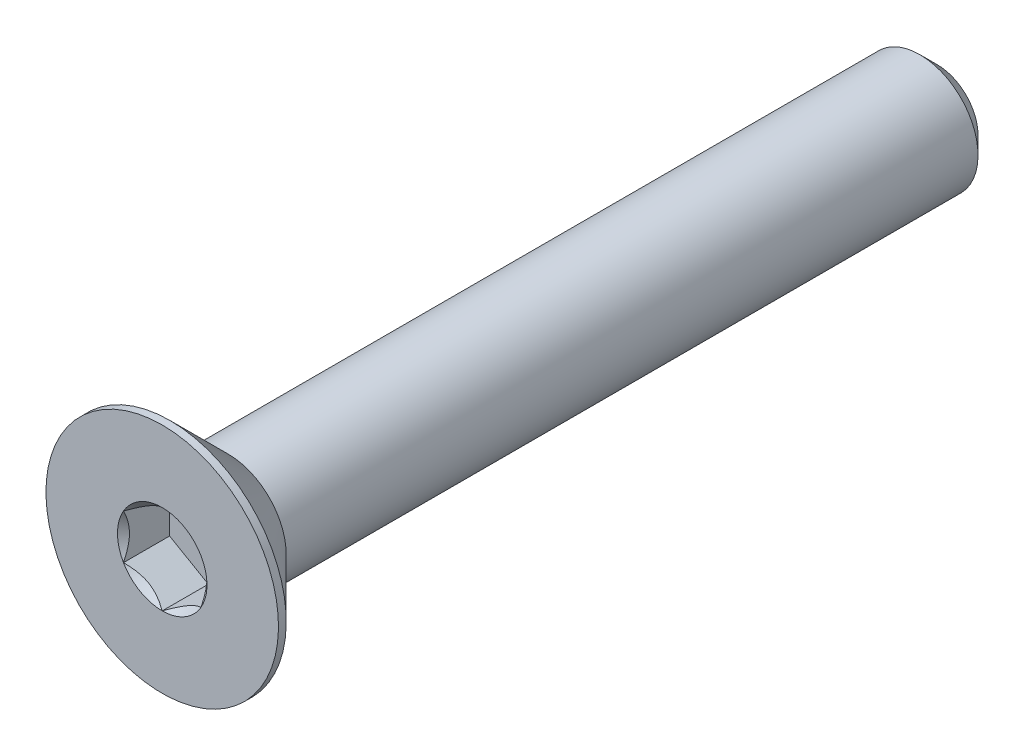
SolidWorks part; units mm, degrees
material "Alloy Steel"
ref_plane "Front" through (0, 0, 0) normal (0, 0, 1) x (1, 0, 0)
ref_plane "Top" through (0, 0, 0) normal (0, 1, 0) x (1, 0, 0)
ref_plane "Right" through (0, 0, 0) normal (1, 0, 0) x (0, 0, -1)
sketch "Sketch1" plane through (0, 0, 0) normal (1, 0, 0) x (0, 0, -1)
  line L0 (-10, 3) -> (-9.8, 3) construction
  line L1 (-9.8, 3) -> (-8.3, 1.5) construction
  line L2 (-10, 1.5) -> (10, 1.5) construction
  line L3 (10, 1.5) -> (10, 0) construction
  line L4 (10, 0) -> (-10, 0) construction
  line L5 (-10, 0) -> (-10, 3) construction
  line L6 (-10, 3) -> (-10, -3) construction
  line L7 (10, 1.5) -> (10, -1.5) construction
  line L8 (-10, -3) -> (-9.8, -3) construction
  line L9 (-9.8, -3) -> (-8.3, -1.5) construction
  line L11 (-10, 1.5) -> (-10, 0) construction
  line L12 (-8.3, 1.5) -> (-8.3, 0) construction
  line L13 (9.9688, 1.5541) -> (10.2188, 1.1211) construction
  line L14 (10.2188, 1.1211) -> (10.4688, 1.5541) construction
  line L15 (10.4688, 1.5541) -> (9.9688, 1.5541) construction
  line L16 (10.2188, 1.5541) -> (10.2188, 1.5) construction
  line L17 (10.2188, 1.5) -> (10.2188, 1.1752) construction
  line L18 (10.2188, 1.1752) -> (10.2188, 1.1211) construction
  line L19 (10.2188, 1.5271) -> (10.4531, 1.5271) construction
  line L20 (10.2188, 1.5271) -> (9.9844, 1.5271) construction
  line L21 (10, 1.5) -> (10.4375, 1.5) construction
  line L22 (10.1875, 1.1752) -> (10.25, 1.1752) construction
  line L23 (10, -1.5) -> (-8.3, -1.5) construction
  point P10 (8.75, -1.5)
  point P24 (-8.3, 1.5)
  point P30 (0, 0)
  dimension "Head Diameter" = 6
  dimension "Head Height" = 1.7
  dimension "Length" = 20
  dimension "Countersink Angle" = 90
  dimension "Thread Pitch" = 0.5
  dimension "D2" = 0.0625
  dimension "Minimum Thread Length" = 18.3
  dimension "Thread Size" = 3
  dimension "D1" = 1.25
sketch "Sketch2" plane through (0, 0, 0) normal (0, 0, 1) x (1, 0, 0)
  line L1 (0, 1.1547) -> (-1, 0.5774) construction
  line L2 (-1, 0.5774) -> (-1, -0.5774) construction
  line L3 (-1, -0.5774) -> (0, -1.1547) construction
  line L4 (0, -1.1547) -> (1, -0.5774) construction
  line L5 (1, -0.5774) -> (1, 0.5774) construction
  line L6 (1, 0.5774) -> (0, 1.1547) construction
  circle A0 centre (0, 0) radius 1 construction
  dimension "Drive Size" = 2
sketch "Sketch3" plane through (0, 0, 0) normal (1, 0, 0) x (0, 0, -1)
  line L0 (-10, 1.5) -> (10, 1.5)
  line L1 (10, 1.5) -> (10, 0)
  line L2 (10, 0) -> (-10, 0)
  line L3 (-10, 0) -> (-10, 1.5)
revolve "Revolve1" add sketch "Sketch3" angle 360 about L4
chamfer "Chamfer1" distance 0.45 angle 45 1 edges at (0, 1.5, -10)
sketch "Sketch6" plane through (0, 0, 0) normal (1, 0, 0) x (0, 0, -1)
  line L0 (-10, 3) -> (-9.8, 3)
  line L1 (-9.8, 3) -> (-8.3, 1.5)
  line L2 (-8.3, 1.5) -> (-8.3, 0)
  line L3 (-8.3, 0) -> (-10, 0)
  line L4 (-10, 0) -> (-10, 3)
revolve "Revolve2" add sketch "Sketch6" angle 360 about L4
sketch "Sketch8" plane through (0, 0, 10) normal (0, 0, 1) x (1, 0, 0)
  line L0 (0, 1.1547) -> (-1, 0.5774) construction
  line L1 (1, 0.5774) -> (0, 1.1547) construction
  line L2 (1, -0.5774) -> (1, 0.5774) construction
  line L3 (0, -1.1547) -> (1, -0.5774) construction
  line L4 (-1, 0.5774) -> (-1, -0.5774) construction
  line L5 (-1, -0.5774) -> (0, -1.1547) construction
  line L6 (0, 1.1547) -> (-1, 0.5774)
  line L7 (1, 0.5774) -> (0, 1.1547)
  line L8 (1, -0.5774) -> (1, 0.5774)
  line L9 (0, -1.1547) -> (1, -0.5774)
  line L10 (-1, 0.5774) -> (-1, -0.5774)
  line L11 (-1, -0.5774) -> (0, -1.1547)
extrude "Cut-Extrude1" cut sketch "Sketch8" against normal blind 1.19
sketch "Sketch9" plane through (0, 0, 10) normal (0, 0, 1) x (1, 0, 0)
  circle A0 centre (0, 0) radius 1.1547
extrude "Cut-Extrude2" cut sketch "Sketch9" against normal up to next (1.19 mm away) draft 45
ref_plane "Plane1" [suppressed] through (0, 0, 8.3) normal (0, 0, 1) x (1, 0, 0)
split "Split1" [suppressed] bodies to split 124
sketch "Sketch4" [suppressed] plane through (0, 0, -10) normal (0, 0, -1) x (-1, 0, 0)
  circle A0 centre (0, 0) radius 1.5 construction
  circle A1 centre (0, 0) radius 1.5
curve "Helix/Spiral1" [suppressed] pitch 0.5 height 18.8 turns 37.6
sketch "Sketch10" [suppressed] plane through (0, 0, 0) normal (1, 0, 0) x (0, 0, -1)
  line L0 (9.9844, 1.5271) -> (10.4531, 1.5271)
  line L1 (10.4531, 1.5271) -> (10.25, 1.1752)
  line L2 (10.25, 1.1752) -> (10.1875, 1.1752)
  line L3 (10.1875, 1.1752) -> (9.9844, 1.5271)
sweep "Cut-Sweep1" [suppressed] cut profiles "Sketch10" path "Helix/Spiral1"
equation "\"D2@Sketch1\" = \"Thread Pitch@Sketch1\" / 8"
equation "\"D4@Helix/Spiral1\"=\"Thread Pitch@Sketch1\""
equation "\"D3@Helix/Spiral1\"=\"Minimum Thread Length@Sketch1\"+\"Thread Pitch@Sketch1\""
equation "\"D1@Chamfer1\"=\"Thread Size@Sketch1\"*.15"
equation "\"D1@Cut-Extrude1\"=\"Head Height@Sketch1\"*.7"
equation "\"D1@Sketch1\"=\"Thread Pitch@Sketch1\"*2.5"
